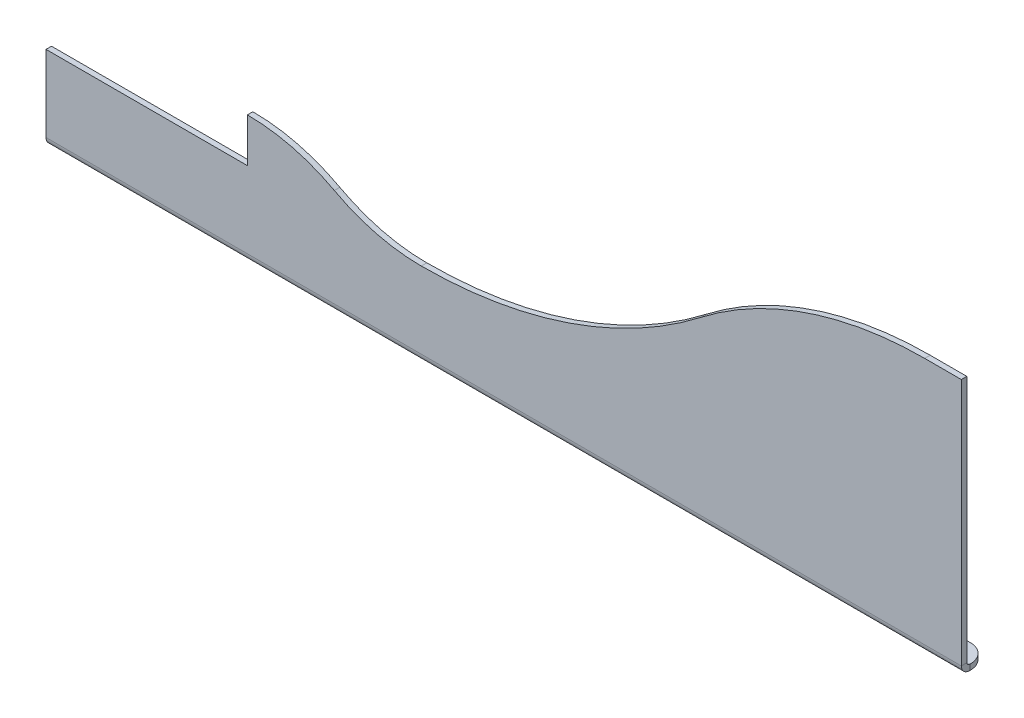
SolidWorks part; units mm, degrees
note: The reader was unsure of these and kept them because the rebuilt part matched: thickness of "Basis-Blech1"; flange length of "Kante-Lasche1".
material "AISI Typ 316L Edelstahl"
ref_plane "Ebene vorne" through (0, 0, 0) normal (0, 0, 1) x (1, 0, 0)
ref_plane "Ebene oben" through (0, 0, 0) normal (0, 1, 0) x (1, 0, 0)
ref_plane "Ebene rechts" through (0, 0, 0) normal (1, 0, 0) x (0, 0, -1)
sketch "Skizze9" plane through (0, 0, 0) normal (0, 0, 1) x (1, 0, 0)
  line L0 (-4.1078, 21.0199) -> (495.8922, 21.0199)
  line L1 (495.8922, 21.0199) -> (495.8922, 161.0199)
  line L2 (-4.1078, 21.0199) -> (-4.1078, 67.215)
  line L4 (495.8922, 161.0199) -> (475.8922, 161.0199)
  line L5 (245.8922, 21.0199) -> (245.8922, 263.8544) construction
  line L6 (475.8922, -38.9801) -> (475.8922, 202.5337) construction
  line L7 (200.8922, 317.215) -> (200.8922, 36.6353) construction
  line L12 (105.8922, 91.2179) -> (105.8922, 67.215)
  line L13 (105.8922, 67.215) -> (-4.1078, 67.215)
  line L14 (200.8922, 67.215) -> (181.5753, 67.215) construction
  line L15 (105.8922, 91.2179) -> (159.2037, 91.2179) construction
  arc A9 (475.8922, 161.0199) -> (353.67, 119.3288) centre (475.8922, -38.9801) ccw
  arc A10 (353.67, 119.3288) -> (200.8922, 67.215) centre (200.8922, 317.215) cw
  arc A11 (200.8922, 67.215) -> (153.3922, 79.2165) centre (200.8922, 167.215) cw
  arc A12 (153.3922, 79.2165) -> (105.8922, 91.2179) centre (105.8922, -8.7821) ccw
  dimension "D4" = 200
  dimension "D3" = 20
  dimension "D13" = 250
  dimension "D15" = 24.0028
  dimension "D2" = 100
  dimension "D8" = 100
  dimension "D1" = 500
  dimension "D5" = 142.2222
  dimension "D6" = 41.691
  dimension "D7" = 295
  dimension "D9" = 390
  dimension "D10" = 110
  dimension "D11" = 95
  dimension "D12" = 140
  dimension "D14" = 46.1952
base flange "Basis-Blech1" sketch "Skizze9" thickness 3 parameters "D1"=1.5
bend "Basisbiegung1" bend radius 4.5 bend angle 90 parameters "D5"=1
bend "Basisbiegung2" bend radius 1.5 bend angle 90 parameters "D5"=2
bend "Basisbiegung3" bend radius 1.5 bend angle 90 parameters "D5"=3
bend "Basisbiegung4" bend radius 1.5 bend angle 90 parameters "D5"=4
bend "Basisbiegung5" bend radius 1.5 bend angle 90 parameters "D5"=5
bend "Basisbiegung6" bend radius 200 bend angle 41.417 parameters "D5"=6
bend "Basisbiegung7" bend radius 247 bend angle 53.416 parameters "D5"=7, "D2"=20
edge flange "Kante-Lasche1" sketch "Skizze16" flange angle 90 flange length 55 flange position material inside bend radius 1.5 thickness 3 parameters "D6"=10
sketch "Skizze16" plane through (0, 21.0199, -3) normal (0, 1, 0) x (1, 0, 0)
  line L1 (495.8922, 0) -> (-4.1078, 0) construction
  line L2 (-4.1078, 0) -> (-4.1078, 52)
  line L3 (-4.1078, 52) -> (495.8922, 52)
  line L4 (495.8922, 52) -> (495.8922, 0)
  line L5 (495.8922, 0) -> (-4.1078, 0)
bend "Kantenbiegung1" bend radius 1.5 bend angle 90 parameters "D5"=1
sketch "Skizze19" plane through (0, 21.0199, 0) normal (0, -1, 0) x (1, 0, 0)
  line L0 (245.8922, -55) -> (245.8922, 45.9034) construction
  line L1 (245.8922, -29.75) -> (220.6422, -4.5) construction
  line L3 (495.8922, -55) -> (-4.1078, -55) construction
  line L4 (-4.1078, -29.75) -> (495.8922, -29.75) construction
  line L5 (-4.1078, -55) -> (-4.1078, -4.5) construction
  line L6 (495.8922, -4.5) -> (495.8922, -55) construction
  line L7 (245.8922, -29.75) -> (271.1422, -4.5) construction
  line L8 (495.8922, -4.5) -> (-4.1078, -4.5) construction
  circle A4 centre (263.5699, -12.0723) radius 3.1
  circle A8 centre (228.2146, -12.0723) radius 3.1
  circle A9 centre (263.5699, -47.4277) radius 3.1
  circle A10 centre (228.2146, -47.4277) radius 3.1
  point P25 (250.3305, -28.5239)
  dimension "D2" = 25
  dimension "D1" = 6.2
  dimension "D5" = 6.2
  dimension "D4" = 25
  dimension "D3" = 45
  dimension "D6" = 50
extrude "Schnitt-Linear austragen2" cut sketch "Skizze19" against normal through all
sketch "Skizze21" plane through (0, 21.0199, 0) normal (0, -1, 0) x (1, 0, 0)
  line L0 (-4.1078, -55) -> (-4.1078, -15)
  line L1 (-4.1078, -55) -> (-4.1078, -4.5) construction
  line L2 (-4.1078, -15) -> (183.5316, -15)
  line L3 (201.4201, -26.0557) -> (215.8922, -55)
  line L4 (495.8922, -55) -> (-4.1078, -55) construction
  line L5 (215.8922, -55) -> (-4.1078, -55)
  line L6 (245.8922, 0) -> (245.8922, -55) construction
  line L7 (-4.1078, 0) -> (495.8922, 0) construction
  line L8 (275.8922, -55) -> (495.8922, -55)
  line L9 (290.3644, -26.0557) -> (275.8922, -55)
  line L10 (495.8922, -15) -> (308.2529, -15)
  line L11 (495.8922, -55) -> (495.8922, -15)
  arc A0 (201.4201, -26.0557) -> (183.5316, -15) centre (183.5316, -35) ccw
  arc A1 (290.3644, -26.0557) -> (308.2529, -15) centre (308.2529, -35) cw
  point P15 (195.8922, -15)
  point P22 (295.8922, -15)
  dimension "D4" = 20
  dimension "D1" = 40
  dimension "D2" = 220
  dimension "D3" = 200
extrude "Schnitt-Linear austragen3" cut sketch "Skizze21" against normal through all
fillet "Verrundung1" radius 10 4 edges at (495.8922, 22.5199, -15) (275.8922, 22.5199, -55) (215.8922, 22.5199, -55) (-4.1078, 22.5199, -15)
unfold "Entfalten2"
sketch "Skizze19-1" plane through (0, 25.3075, 0) normal (0, 0, 1) x (1, 0, 0)
  line L0 (245.8922, -55) -> (245.8922, 45.9034) construction
  line L1 (245.8922, -29.75) -> (220.6422, -4.5) construction
  line L4 (-4.1078, -29.75) -> (495.8922, -29.75) construction
  line L7 (245.8922, -29.75) -> (271.1422, -4.5) construction
  circle A4 centre (263.5699, -12.0723) radius 3.1
  circle A8 centre (228.2146, -12.0723) radius 3.1
  circle A9 centre (263.5699, -47.4277) radius 3.1
  circle A10 centre (228.2146, -47.4277) radius 3.1
  point P25 (250.3305, -28.5239)
  dimension "D2" = 25
  dimension "D1" = 6.2
  dimension "D5" = 6.2
  dimension "D4" = 25
  dimension "D3" = 45
  dimension "D6" = 50
sketch "Skizze21-1" plane through (0, 25.3075, 0) normal (0, 0, 1) x (1, 0, 0)
  line L0 (-4.1078, -55) -> (-4.1078, -15)
  line L2 (-4.1078, -15) -> (183.5316, -15)
  line L3 (201.4201, -26.0557) -> (215.8922, -55)
  line L5 (215.8922, -55) -> (-4.1078, -55)
  line L6 (245.8922, 0) -> (245.8922, -55) construction
  line L8 (275.8922, -55) -> (495.8922, -55)
  line L9 (290.3644, -26.0557) -> (275.8922, -55)
  line L10 (495.8922, -15) -> (308.2529, -15)
  line L11 (495.8922, -55) -> (495.8922, -15)
  arc A0 (201.4201, -26.0557) -> (183.5316, -15) centre (183.5316, -35) ccw
  arc A1 (290.3644, -26.0557) -> (308.2529, -15) centre (308.2529, -35) cw
  point P15 (195.8922, -15)
  point P22 (295.8922, -15)
  dimension "D4" = 20
  dimension "D1" = 40
  dimension "D2" = 220
  dimension "D3" = 200
fold "Falten1"
sketch "Skizze19-2" plane through (0, 21.0199, 0) normal (0, -1, 0) x (1, 0, 0)
  line L0 (245.8922, -55) -> (245.8922, 45.9034) construction
  line L1 (245.8922, -29.75) -> (220.6422, -4.5) construction
  line L4 (-4.1078, -29.75) -> (495.8922, -29.75) construction
  line L7 (245.8922, -29.75) -> (271.1422, -4.5) construction
  circle A4 centre (263.5699, -12.0723) radius 3.1
  circle A8 centre (228.2146, -12.0723) radius 3.1
  circle A9 centre (263.5699, -47.4277) radius 3.1
  circle A10 centre (228.2146, -47.4277) radius 3.1
  point P25 (250.3305, -28.5239)
  dimension "D2" = 25
  dimension "D1" = 6.2
  dimension "D5" = 6.2
  dimension "D4" = 25
  dimension "D3" = 45
  dimension "D6" = 50
sketch "Skizze21-2" plane through (0, 21.0199, 0) normal (0, -1, 0) x (1, 0, 0)
  line L0 (-4.1078, -55) -> (-4.1078, -15)
  line L2 (-4.1078, -15) -> (183.5316, -15)
  line L3 (201.4201, -26.0557) -> (215.8922, -55)
  line L5 (215.8922, -55) -> (-4.1078, -55)
  line L6 (245.8922, 0) -> (245.8922, -55) construction
  line L8 (275.8922, -55) -> (495.8922, -55)
  line L9 (290.3644, -26.0557) -> (275.8922, -55)
  line L10 (495.8922, -15) -> (308.2529, -15)
  line L11 (495.8922, -55) -> (495.8922, -15)
  arc A0 (201.4201, -26.0557) -> (183.5316, -15) centre (183.5316, -35) ccw
  arc A1 (290.3644, -26.0557) -> (308.2529, -15) centre (308.2529, -35) cw
  point P15 (195.8922, -15)
  point P22 (295.8922, -15)
  dimension "D4" = 20
  dimension "D1" = 40
  dimension "D2" = 220
  dimension "D3" = 200
unfold "Entfalten3"
sketch "Skizze19-3" plane through (0, 25.3075, 0) normal (0, 0, 1) x (1, 0, 0)
  line L0 (245.8922, -55) -> (245.8922, 45.9034) construction
  line L1 (245.8922, -29.75) -> (220.6422, -4.5) construction
  line L4 (-4.1078, -29.75) -> (495.8922, -29.75) construction
  line L7 (245.8922, -29.75) -> (271.1422, -4.5) construction
  circle A4 centre (263.5699, -12.0723) radius 3.1
  circle A8 centre (228.2146, -12.0723) radius 3.1
  circle A9 centre (263.5699, -47.4277) radius 3.1
  circle A10 centre (228.2146, -47.4277) radius 3.1
  point P25 (250.3305, -28.5239)
  dimension "D2" = 25
  dimension "D1" = 6.2
  dimension "D5" = 6.2
  dimension "D4" = 25
  dimension "D3" = 45
  dimension "D6" = 50
sketch "Skizze21-3" plane through (0, 25.3075, 0) normal (0, 0, 1) x (1, 0, 0)
  line L0 (-4.1078, -55) -> (-4.1078, -15)
  line L2 (-4.1078, -15) -> (183.5316, -15)
  line L3 (201.4201, -26.0557) -> (215.8922, -55)
  line L5 (215.8922, -55) -> (-4.1078, -55)
  line L6 (245.8922, 0) -> (245.8922, -55) construction
  line L8 (275.8922, -55) -> (495.8922, -55)
  line L9 (290.3644, -26.0557) -> (275.8922, -55)
  line L10 (495.8922, -15) -> (308.2529, -15)
  line L11 (495.8922, -55) -> (495.8922, -15)
  arc A0 (201.4201, -26.0557) -> (183.5316, -15) centre (183.5316, -35) ccw
  arc A1 (290.3644, -26.0557) -> (308.2529, -15) centre (308.2529, -35) cw
  point P15 (195.8922, -15)
  point P22 (295.8922, -15)
  dimension "D4" = 20
  dimension "D1" = 40
  dimension "D2" = 220
  dimension "D3" = 200
fold "Falten2"
sketch "Skizze19-4" plane through (0, 21.0199, 0) normal (0, -1, 0) x (1, 0, 0)
  line L0 (245.8922, -55) -> (245.8922, 45.9034) construction
  line L1 (245.8922, -29.75) -> (220.6422, -4.5) construction
  line L4 (-4.1078, -29.75) -> (495.8922, -29.75) construction
  line L7 (245.8922, -29.75) -> (271.1422, -4.5) construction
  circle A4 centre (263.5699, -12.0723) radius 3.1
  circle A8 centre (228.2146, -12.0723) radius 3.1
  circle A9 centre (263.5699, -47.4277) radius 3.1
  circle A10 centre (228.2146, -47.4277) radius 3.1
  point P25 (250.3305, -28.5239)
  dimension "D2" = 25
  dimension "D1" = 6.2
  dimension "D5" = 6.2
  dimension "D4" = 25
  dimension "D3" = 45
  dimension "D6" = 50
sketch "Skizze21-4" plane through (0, 21.0199, 0) normal (0, -1, 0) x (1, 0, 0)
  line L0 (-4.1078, -55) -> (-4.1078, -15)
  line L2 (-4.1078, -15) -> (183.5316, -15)
  line L3 (201.4201, -26.0557) -> (215.8922, -55)
  line L5 (215.8922, -55) -> (-4.1078, -55)
  line L6 (245.8922, 0) -> (245.8922, -55) construction
  line L8 (275.8922, -55) -> (495.8922, -55)
  line L9 (290.3644, -26.0557) -> (275.8922, -55)
  line L10 (495.8922, -15) -> (308.2529, -15)
  line L11 (495.8922, -55) -> (495.8922, -15)
  arc A0 (201.4201, -26.0557) -> (183.5316, -15) centre (183.5316, -35) ccw
  arc A1 (290.3644, -26.0557) -> (308.2529, -15) centre (308.2529, -35) cw
  point P15 (195.8922, -15)
  point P22 (295.8922, -15)
  dimension "D4" = 20
  dimension "D1" = 40
  dimension "D2" = 220
  dimension "D3" = 200
unfold "Entfalten4"
sketch "Skizze19-5" plane through (0, 25.3075, 0) normal (0, 0, 1) x (1, 0, 0)
  line L0 (245.8922, -55) -> (245.8922, 45.9034) construction
  line L1 (245.8922, -29.75) -> (220.6422, -4.5) construction
  line L4 (-4.1078, -29.75) -> (495.8922, -29.75) construction
  line L7 (245.8922, -29.75) -> (271.1422, -4.5) construction
  circle A4 centre (263.5699, -12.0723) radius 3.1
  circle A8 centre (228.2146, -12.0723) radius 3.1
  circle A9 centre (263.5699, -47.4277) radius 3.1
  circle A10 centre (228.2146, -47.4277) radius 3.1
  point P25 (250.3305, -28.5239)
  dimension "D2" = 25
  dimension "D1" = 6.2
  dimension "D5" = 6.2
  dimension "D4" = 25
  dimension "D3" = 45
  dimension "D6" = 50
sketch "Skizze21-5" plane through (0, 25.3075, 0) normal (0, 0, 1) x (1, 0, 0)
  line L0 (-4.1078, -55) -> (-4.1078, -15)
  line L2 (-4.1078, -15) -> (183.5316, -15)
  line L3 (201.4201, -26.0557) -> (215.8922, -55)
  line L5 (215.8922, -55) -> (-4.1078, -55)
  line L6 (245.8922, 0) -> (245.8922, -55) construction
  line L8 (275.8922, -55) -> (495.8922, -55)
  line L9 (290.3644, -26.0557) -> (275.8922, -55)
  line L10 (495.8922, -15) -> (308.2529, -15)
  line L11 (495.8922, -55) -> (495.8922, -15)
  arc A0 (201.4201, -26.0557) -> (183.5316, -15) centre (183.5316, -35) ccw
  arc A1 (290.3644, -26.0557) -> (308.2529, -15) centre (308.2529, -35) cw
  point P15 (195.8922, -15)
  point P22 (295.8922, -15)
  dimension "D4" = 20
  dimension "D1" = 40
  dimension "D2" = 220
  dimension "D3" = 200
fold "Falten3"
sketch "Skizze19-6" plane through (0, 21.0199, 0) normal (0, -1, 0) x (1, 0, 0)
  line L0 (245.8922, -55) -> (245.8922, 45.9034) construction
  line L1 (245.8922, -29.75) -> (220.6422, -4.5) construction
  line L4 (-4.1078, -29.75) -> (495.8922, -29.75) construction
  line L7 (245.8922, -29.75) -> (271.1422, -4.5) construction
  circle A4 centre (263.5699, -12.0723) radius 3.1
  circle A8 centre (228.2146, -12.0723) radius 3.1
  circle A9 centre (263.5699, -47.4277) radius 3.1
  circle A10 centre (228.2146, -47.4277) radius 3.1
  point P25 (250.3305, -28.5239)
  dimension "D2" = 25
  dimension "D1" = 6.2
  dimension "D5" = 6.2
  dimension "D4" = 25
  dimension "D3" = 45
  dimension "D6" = 50
sketch "Skizze21-6" plane through (0, 21.0199, 0) normal (0, -1, 0) x (1, 0, 0)
  line L0 (-4.1078, -55) -> (-4.1078, -15)
  line L2 (-4.1078, -15) -> (183.5316, -15)
  line L3 (201.4201, -26.0557) -> (215.8922, -55)
  line L5 (215.8922, -55) -> (-4.1078, -55)
  line L6 (245.8922, 0) -> (245.8922, -55) construction
  line L8 (275.8922, -55) -> (495.8922, -55)
  line L9 (290.3644, -26.0557) -> (275.8922, -55)
  line L10 (495.8922, -15) -> (308.2529, -15)
  line L11 (495.8922, -55) -> (495.8922, -15)
  arc A0 (201.4201, -26.0557) -> (183.5316, -15) centre (183.5316, -35) ccw
  arc A1 (290.3644, -26.0557) -> (308.2529, -15) centre (308.2529, -35) cw
  point P15 (195.8922, -15)
  point P22 (295.8922, -15)
  dimension "D4" = 20
  dimension "D1" = 40
  dimension "D2" = 220
  dimension "D3" = 200
sketch "Biegung-Linien3" [suppressed] plane through (0, 0, 0) normal (0, 1, 0) x (1, 0, 0)
sketch "Rahmen3" [suppressed] plane through (0, 0, 0) normal (0, 1, 0) x (1, 0, 0)
sheet metal parameters "Blech4" thickness 3 parameters "D1"=1.5
flat pattern "Abwicklung4"
sketch "Biegung-Linien4" plane through (0, 21.0199, 0) normal (0, 1, 0) x (1, 0, 0)
  line L0 (920.8107, -20) -> (920.8107, 0) construction
  line L1 (732.1452, -20) -> (732.1452, 0) construction
  line L2 (638.4608, 0) -> (638.4608, -20) construction
  line L3 (496.7484, 0) -> (496.7484, -20) construction
  line L4 (-4.964, -20) -> (-4.964, 0) construction
  line L5 (-46.6763, -20) -> (-46.6763, 0) construction
  line L6 (-95.3887, -20) -> (-95.3887, 0) construction
  line L7 (920.8107, -20) -> (920.8107, 0) construction
  line L8 (732.1452, -20) -> (732.1452, 0) construction
  line L9 (638.4608, 0) -> (638.4608, -20) construction
  line L10 (496.7484, 0) -> (496.7484, -20) construction
  line L11 (-4.964, -20) -> (-4.964, 0) construction
  line L12 (-46.6763, -20) -> (-46.6763, 0) construction
  line L13 (-95.3887, -20) -> (-95.3887, 0) construction
sketch3d "Rahmen4" [suppressed]
  line L0 (-99.1372, 0, 0) -> (-99.1372, 20, 0) construction
  line L1 (1040.7558, 0, 0) -> (1040.7558, 20, 0) construction
  line L2 (-99.1372, 0, 0) -> (1040.7558, 0, 0) construction
  line L3 (-99.1372, 20, 0) -> (1040.7558, 20, 0) construction
sheet metal parameters "Blech5" thickness 3 parameters "D1"=1.5
flat pattern "Abwicklung4"
sketch "Biegung-Linien4" plane through (0, 0, 0) normal (0, 0, 1) x (1, 0, 0)
  line L0 (0, 2.1438) -> (500, 2.1438) construction
  line L1 (0, 2.1438) -> (500, 2.1438) construction
sketch3d "Rahmen4" [suppressed]
  line L0 (-202.6518, -283.9175, 0) -> (297.3482, -283.9175, 0) construction
  line L1 (-202.6518, -88.2051, 0) -> (297.3482, -88.2051, 0) construction
  line L2 (-202.6518, -283.9175, 0) -> (-202.6518, -88.2051, 0) construction
  line L3 (297.3482, -283.9175, 0) -> (297.3482, -88.2051, 0) construction
bend of the flat pattern "Abwickeln-<Kantenbiegung1>1"
sheet metal parameters "Blech6" thickness 3 parameters "D1"=1.5
flat pattern "Abwicklung4"
sketch "Biegung-Linien4" plane through (0, 0, 0) normal (0, 0, 1) x (1, 0, 0)
  line L0 (0, 2.1438) -> (500, 2.1438) construction
  line L1 (0, 2.1438) -> (500, 2.1438) construction
sketch3d "Rahmen4" [suppressed]
  line L0 (297.3482, -278.9175, 0) -> (297.3482, -88.2051, 0) construction
  line L1 (-202.6518, -278.9175, 0) -> (-202.6518, -88.2051, 0) construction
  line L2 (297.3482, -278.9175, 0) -> (-202.6518, -278.9175, 0) construction
  line L3 (297.3482, -88.2051, 0) -> (-202.6518, -88.2051, 0) construction
bend of the flat pattern "Abwickeln-<Kantenbiegung1>1"
sheet metal parameters "Blech7" thickness 3 parameters "D1"=1.5
flat pattern "Abwicklung4"
sketch "Biegung-Linien4" plane through (0, 0, 0) normal (0, 0, 1) x (1, 0, 0)
  line L0 (-4.1078, 23.1637) -> (495.8922, 23.1637) construction
  line L1 (-4.1078, 23.1637) -> (495.8922, 23.1637) construction
sketch3d "Rahmen4" [suppressed]
  line L0 (-110, -20.9104, 0) -> (-110, 169.802, 0) construction
  line L1 (390, -20.9104, 0) -> (390, 169.802, 0) construction
  line L2 (-110, -20.9104, 0) -> (390, -20.9104, 0) construction
  line L3 (-110, 169.802, 0) -> (390, 169.802, 0) construction
bend of the flat pattern "Abwickeln-<Kantenbiegung1>1"
